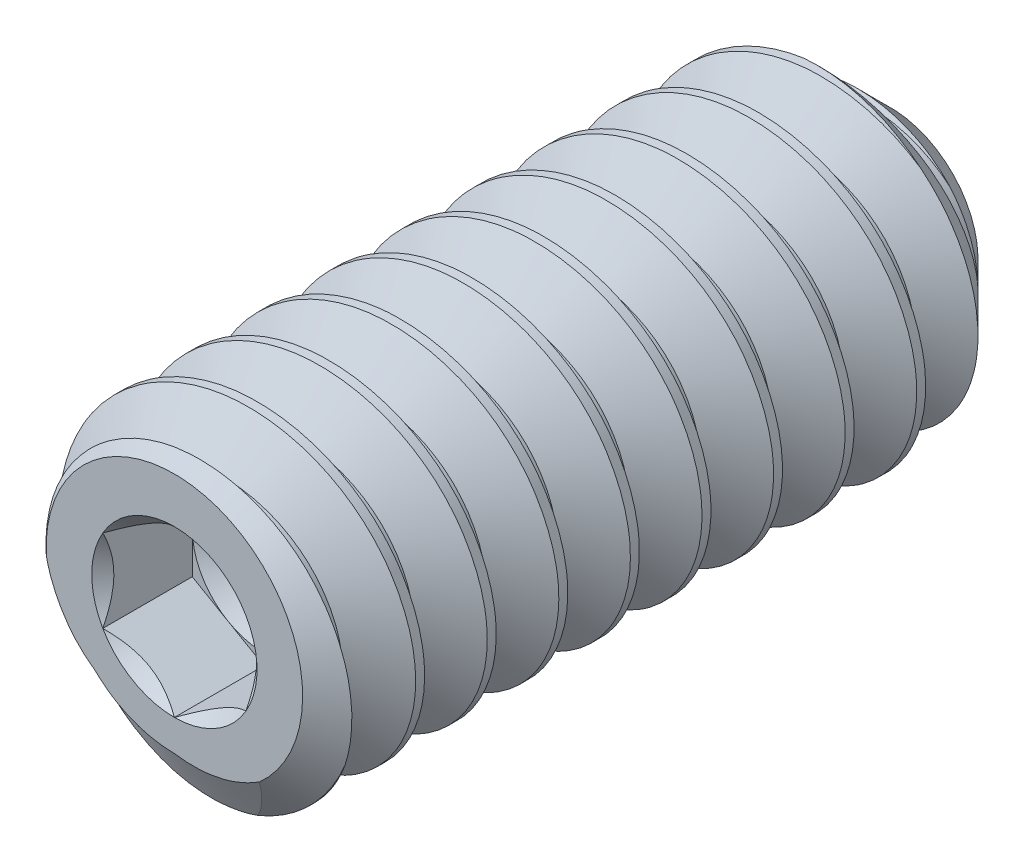
SolidWorks part; units mm, degrees
ref_plane "Front" through (0, 0, 0) normal (0, 0, 1) x (1, 0, 0)
ref_plane "Top" through (0, 0, 0) normal (0, 1, 0) x (1, 0, 0)
ref_plane "Right" through (0, 0, 0) normal (1, 0, 0) x (0, 0, -1)
sketch "Sketch22" plane through (0, 0, 0) normal (1, 0, 0) x (0, 0, -1)
  line L0 (-2.9408, 0) -> (-2.9408, 1.1379)
  line L1 (-2.9408, 1.1379) -> (-2.7416, 1.4224)
  line L2 (-2.7416, 1.4224) -> (2.7662, 1.4224)
  line L3 (2.7662, 1.4224) -> (3.4092, 0.7794)
  line L4 (3.4092, 0.7794) -> (2.9408, 0) construction
  line L5 (2.9408, 0) -> (-2.9408, 0)
  line L6 (2.9408, 0) -> (3.4092, 0) construction
  line L7 (3.4092, 0) -> (3.4092, 0.7794) construction
  line L8 (3.4092, -0.7794) -> (2.9408, 0) construction
  line L9 (-2.7416, -1.4224) -> (2.7662, -1.4224) construction
  line L10 (3.4092, 0.7794) -> (3.4092, 0)
  line L11 (3.4092, 0) -> (2.9408, 0)
  dimension "Dia" = 2.8448
  dimension "Length" = 6.35
  dimension "D3" = 35
  dimension "D5" = 118
  dimension "D6" = 45
  dimension "D7" = 2.2758
revolve "Revolve1" add sketch "Sketch22" angle 360 about L6
ref_plane "Plane1" through (0, 0, -3.4092) normal (0, 0, 1) x (1, 0, 0)
sketch "Sketch27" plane through (0, 0, -3.4092) normal (0, 0, 1) x (1, 0, 0)
  circle A0 centre (0, 0) radius 1.4224 construction
  circle A1 centre (0, 0) radius 1.4224
curve "Helix/Spiral1" pitch 0.635 height 6.985 radius 1.4224 centre (0, 0, -3.4092) axis (0, 0, 1) start towards (0, 1, 0)
sketch "Sketch28" plane through (0, 0, 0) normal (1, 0, 0) x (0, 0, -1)
  line L0 (3.4092, 1.4224) -> (3.9648, 1.4224)
  line L1 (3.9648, 1.4224) -> (3.7267, 1.01)
  line L2 (3.7267, 1.01) -> (3.6473, 1.01)
  line L3 (3.6473, 1.01) -> (3.4092, 1.4224)
  line L4 (3.5282, 1.2162) -> (3.8457, 1.2162) construction
  line L6 (-2.7416, 1.4224) -> (2.7662, 1.4224) construction
  line L7 (3.4092, 6.985) -> (3.4092, -6.985) construction
  dimension "D1" = 0.0794
  dimension "D2" = 0.3175
  dimension "D3" = 60
sweep "Cut-Sweep2" cut profiles "Sketch28" path "Helix/Spiral1" align with end faces yes
sketch "Sketch23" plane through (0, 0, 2.9408) normal (0, 0, 1) x (1, 0, 0)
  line L1 (0, 0.7332) -> (-0.635, 0.3666)
  line L2 (-0.635, 0.3666) -> (-0.635, -0.3666)
  line L3 (-0.635, -0.3666) -> (0, -0.7332)
  line L4 (0, -0.7332) -> (0.635, -0.3666)
  line L5 (0.635, -0.3666) -> (0.635, 0.3666)
  line L6 (0.635, 0.3666) -> (0, 0.7332)
  circle A0 centre (0, 0) radius 0.635 construction
  dimension "Hex" = 1.27
extrude "Cut-Extrude10" cut sketch "Sketch23" against normal blind 0.7937
sketch "Sketch24" plane through (0, 0, 2.9408) normal (0, 0, 1) x (1, 0, 0)
  circle A0 centre (0, 0) radius 0.7332
extrude "Cut-Extrude11" cut sketch "Sketch24" against normal through all draft 45
sketch "Sketch26" plane through (0, 0, 2.1471) normal (0, 0, 1) x (1, 0, 0)
  circle A0 centre (0, 0) radius 0.635 construction
  circle A1 centre (0, 0) radius 0.635
extrude "Cut-Extrude12" cut sketch "Sketch26" against normal through all draft 60
sketch "Sketch30" plane through (0, 0, 0) normal (1, 0, 0) x (0, 0, -1)
  line L0 (-2.7416, 1.4224) -> (2.7662, 1.4224) construction
  line L1 (-2.9408, 0) -> (-2.9408, 1.1379) construction
  line L2 (3.4092, 0) -> (3.4092, 0.7794) construction
  line L3 (-2.7416, -1.4224) -> (2.7662, -1.4224) construction
  point P0 (-2.9408, 1.4224)
  point P1 (3.4092, 1.4224)
  point P2 (3.4092, -1.4224)
  point P11 (1.1867, -1.4224)
  dimension "D1" = 2.2225
sketch "Sketch31" plane through (0, 0, 0) normal (1, 0, 0) x (0, 0, -1)
  line L2 (2.9408, 0) -> (3.4092, -0.7794)
  line L3 (3.4092, 0.7794) -> (2.9408, 0)
equation "\"D7@Sketch22\"=\"Dia@Sketch22\"*.8"
equation "\"D1@Sketch28\" = \"D4@Helix/Spiral1\" * .125"
equation "\"D3@Helix/Spiral1\" = \"Length@Sketch22\" + \"D4@Helix/Spiral1\""
equation "\"D1@Sketch30\" = \"D4@Helix/Spiral1\" * 3.5"
equation "\"hex Depth@Cut-Extrude10\" = \"Hex@Sketch23\" * .625"
equation "\"D2@Sketch28\" = \"D4@Helix/Spiral1\" * .5"
